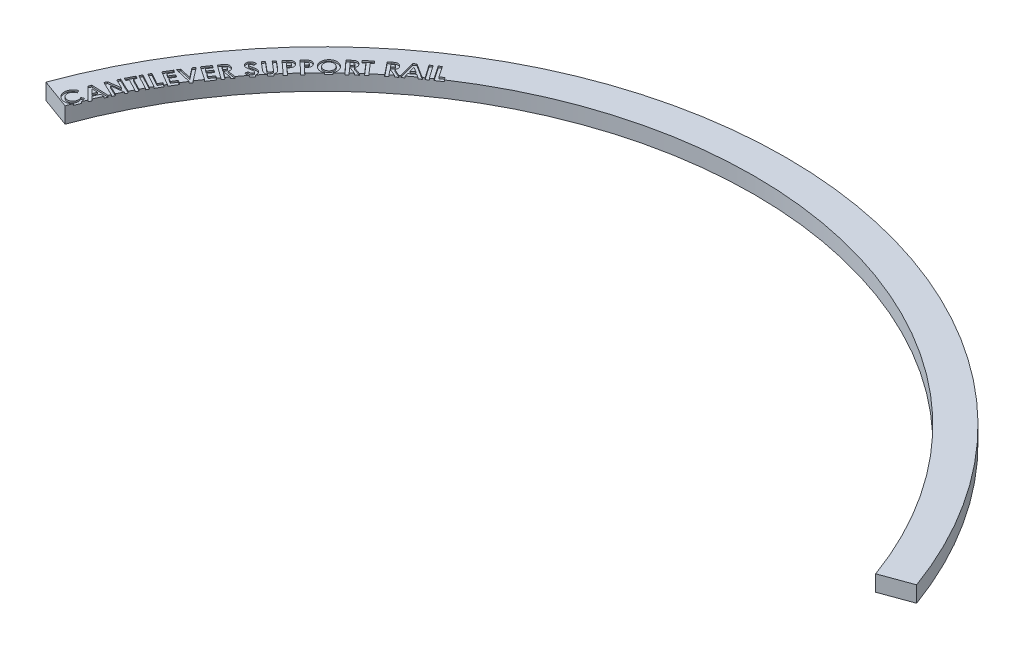
SolidWorks part; units mm, degrees
ref_plane "Front Plane" through (0, 0, 0) normal (0, 0, 1) x (1, 0, 0)
ref_plane "Top Plane" through (0, 0, 0) normal (0, 1, 0) x (1, 0, 0)
ref_plane "Right Plane" through (0, 0, 0) normal (1, 0, 0) x (0, 0, -1)
sketch "Sketch1" plane through (0, 0, 0) normal (0, 1, 0) x (1, 0, 0)
  line L0 (-346.0888, 125.966) -> (-322.2206, 117.2787)
  line L1 (322.2206, 117.2787) -> (346.0888, 125.966)
  line L2 (0, 0) -> (0, 233.0006) construction
  arc A0 (-346.0888, 125.966) -> (346.0888, 125.966) centre (0, 0) cw
  arc A1 (-322.2206, 117.2787) -> (322.2206, 117.2787) centre (0, 0) cw
  point P8 (0, 0)
  point P9 (362.6097, 117.2787)
  point P10 (0, 0)
  point P11 (0, 0)
  point P12 (0, 0)
  point P13 (0, 0)
  dimension "D1" = 342.9
  dimension "D2" = 25.4
  dimension "D3" = 70
  dimension "D4" = 70
extrude "Boss-Extrude1" add sketch "Sketch1" along normal blind 12.7
sketch "Sketch2" plane through (0, 12.7, 0) normal (0, 1, 0) x (1, 0, 0)
  text T0 "CANTILEVER SUPPORT RAIL" font "Century Gothic" height 12.7
extrude "Cut-Extrude1" cut sketch "Sketch2" against normal blind 1.27
